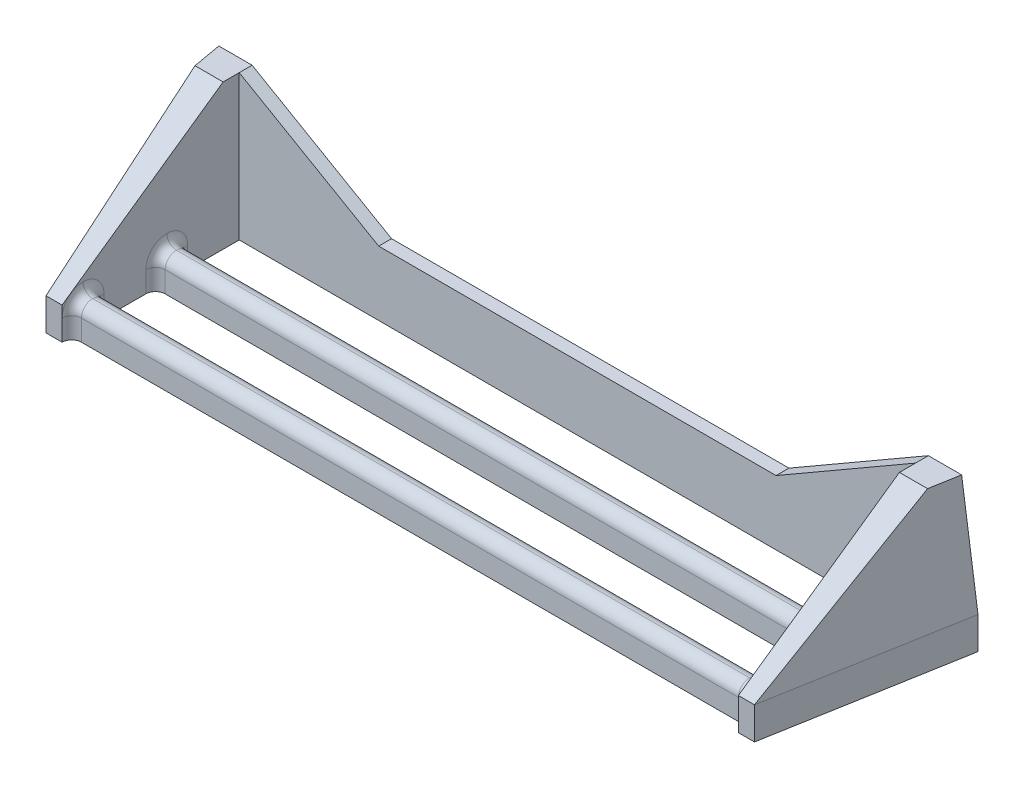
SolidWorks part; units mm, degrees
ref_plane "Vorderansicht" through (0, 0, 0) normal (0, 0, 1) x (1, 0, 0)
ref_plane "Draufsicht" through (0, 0, 0) normal (0, 1, 0) x (1, 0, 0)
ref_plane "Seitenansicht" through (0, 0, 0) normal (1, 0, 0) x (0, 0, -1)
sketch "Skizze1" plane through (0, 0, 0) normal (0, 1, 0) x (1, 0, 0)
  line L0 (-105, -55) -> (-105, 0)
  line L1 (-105, 0) -> (105, 0)
  line L2 (105, 0) -> (105, -55)
  line L3 (105, -55) -> (110, -55)
  line L4 (110, -55) -> (120.4033, 4)
  line L5 (120.4033, 4) -> (-120.4033, 4)
  line L6 (-120.4033, 4) -> (-110, -55)
  line L7 (-110, -55) -> (-105, -55)
  point P8 (-102.2609, 13.3304)
  dimension "D1" = 210
  dimension "D2" = 5
  dimension "D3" = 80
  dimension "D4" = 80
  dimension "D5" = 4
  dimension "D6" = 55
  dimension "D7" = 55
  dimension "D8" = 105
extrude "Aufsatz-Linear austragen1" add sketch "Skizze1" along normal blind 45 contours L0 L1 L2 L3 L4 L5 L6 L7
chamfer "Fase1" distance 35 distance2 50 2 edges at (-107.5, 45, 55) (107.5, 45, 55) first distance on face at (-107.5, 22.5, 55) first distance on face at (107.5, 22.5, 55)
chamfer "Fase2" distance 35 distance2 5 2 edges at (-119.6098, 45, 0.5) (119.6098, 45, 0.5) first distance on face at (-115.9246, 20, 21.4) first distance on face at (115.9246, 20, 21.4)
sketch "Skizze2" plane through (0, 0, 0) normal (0, 0, 1) x (1, 0, 0)
  line L0 (-105, 45) -> (-61.6987, 20)
  line L1 (-61.6987, 20) -> (61.6987, 20)
  line L2 (61.6987, 20) -> (105, 45)
  line L3 (105, 45) -> (-105, 45)
  line L4 (-105, 0) -> (105, 0) construction
  dimension "D1" = 20
  dimension "D2" = 150
  dimension "D3" = 150
extrude "Schnitt-Linear austragen2" cut sketch "Skizze2" against normal through all contours L3 L0 L1 L2
sketch "Skizze4" plane through (0, 0, 0) normal (0, 1, 0) x (1, 0, 0)
  line L0 (-105, -45) -> (105, -45)
  line L1 (-105, -5) -> (-105, -55) construction
  line L3 (105, -45) -> (105, -52)
  line L4 (105, -52) -> (-105, -52)
  line L5 (-105, -52) -> (-105, -45)
  line L6 (-61.6987, 0) -> (61.6987, 0) construction
  line L7 (-105, -26) -> (-105, -19)
  line L8 (-105, -19) -> (105, -19)
  line L9 (105, -19) -> (105, -26)
  line L10 (105, -26) -> (-105, -26)
  line L12 (105, 0) -> (105, -55) construction
  point P12 (0, 0)
  point P15 (0, 0)
  point P16 (0, 0)
  point P17 (0, 0)
  point P18 (0, 0)
  dimension "D1" = 7
  dimension "D2" = 45
  dimension "D3" = 19
  dimension "D4" = 7
extrude "Aufsatz-Linear austragen2" add sketch "Skizze4" along normal blind 10
fillet "Verrundung2" radius 3.5 4 edges at (0, 10, 52) (0, 10, 45) (0, 10, 19) (0, 10, 26)
fillet "Verrundung3" radius 3 16 edges at (-105, 3.25, 52) (-105, 8.9749, 50.9749) (-105, 8.9749, 46.0251) (-105, 3.25, 45) (-105, 3.25, 19) (-105, 8.9749, 20.0251) (-105, 8.9749, 24.9749) (-105, 3.25, 26) (105, 3.25, 45) (105, 8.9749, 46.0251) (105, 8.9749, 50.9749) (105, 3.25, 19) (105, 8.9749, 20.0251) (105, 8.9749, 24.9749) (105, 3.25, 52) (105, 3.25, 26)
